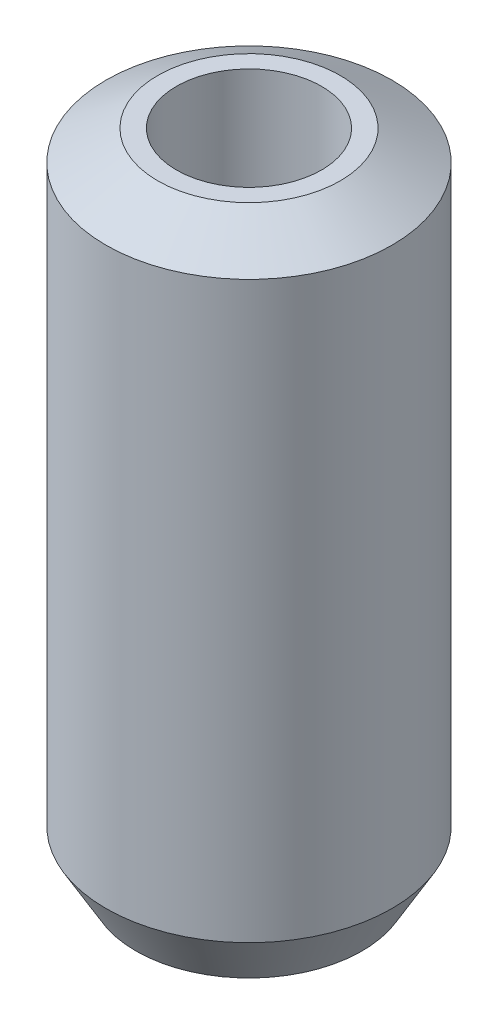
SolidWorks part; units mm, degrees
ref_plane "Front Plane" through (0, 0, 0) normal (0, 0, 1) x (1, 0, 0)
ref_plane "Top Plane" through (0, 0, 0) normal (0, 1, 0) x (1, 0, 0)
ref_plane "Right Plane" through (0, 0, 0) normal (1, 0, 0) x (0, 0, -1)
sketch "Sketch1" plane through (0, 0, 0) normal (0, 1, 0) x (1, 0, 0)
  circle A0 centre (0, 0) radius 7.5
  dimension "SHAFT_OD" = 15
extrude "Boss-Extrude1" add sketch "Sketch1" along normal blind 34.4065
sketch "Sketch2" plane through (0, 0, 0) normal (0, 1, 0) x (1, 0, 0)
  circle A0 centre (0, 0) radius 3.8058
  dimension "BORE_D" = 7.6116
extrude "Cut-Extrude1" cut sketch "Sketch2" along normal through all
chamfer "Chamfer1" distance 1.5661 angle 60 2 edges at (0, 34.4065, 7.5) (0, 0, 7.5) first distance on face at (0, 34.4065, 7.5) first distance on face at (0, 0, 3.8058)
